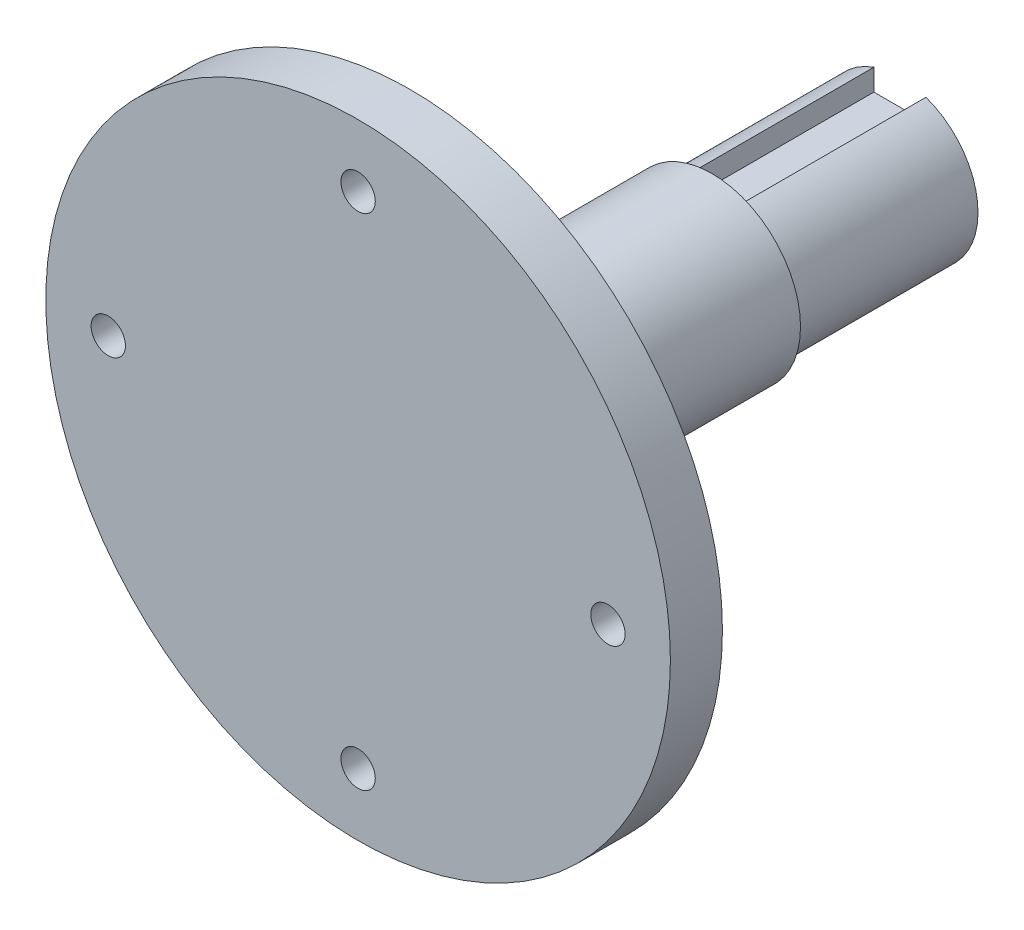
SolidWorks part; units mm, degrees
material "Plain Carbon Steel"
ref_plane "Front Plane" through (0, 0, 0) normal (0, 0, 1) x (1, 0, 0)
ref_plane "Top Plane" through (0, 0, 0) normal (0, 1, 0) x (1, 0, 0)
ref_plane "Right Plane" through (0, 0, 0) normal (1, 0, 0) x (0, 0, -1)
sketch "Sketch1" plane through (0, 0, 0) normal (0, 0, 1) x (1, 0, 0)
  circle A0 centre (0, 0) radius 7.5
  dimension "D1" = 15
extrude "Boss-Extrude1" add sketch "Sketch1" along normal blind 20.05
sketch "Sketch3" plane through (0, 0, 0) normal (0, 0, -1) x (-1, 0, 0)
  line L0 (0, 55) -> (0, -55) construction
  line L1 (-2.5, 5) -> (2.5, 5)
  line L2 (-2.5, 5) -> (-2.5, 10)
  line L3 (-2.5, 10) -> (2.5, 10)
  line L4 (2.5, 5) -> (2.5, 10)
  line L5 (-2.5, 5) -> (2.5, 10) construction
  line L6 (-2.5, 10) -> (2.5, 5) construction
  circle A0 centre (0, 0) radius 7.5 construction
  point P0 (0, 7.5)
  dimension "D1" = 2.5
  dimension "D2" = 5
extrude "Cut-Extrude1" cut sketch "Sketch3" against normal blind 21
sketch "Sketch6" plane through (0, 0, 20.05) normal (0, 0, 1) x (1, 0, 0)
  circle A0 centre (0, 0) radius 8.5
  dimension "D1" = 17
extrude "Boss-Extrude2" add sketch "Sketch6" along normal blind 24
sketch "Sketch7" plane through (0, 0, 44.05) normal (0, 0, 1) x (1, 0, 0)
  circle A0 centre (0, 0) radius 11.25
  dimension "D1" = 22.5
extrude "Boss-Extrude3" add sketch "Sketch7" along normal blind 5
sketch "Sketch8" plane through (0, 0, 49.05) normal (0, 0, 1) x (1, 0, 0)
  circle A0 centre (0, 0) radius 30
  dimension "D1" = 60
extrude "Boss-Extrude4" add sketch "Sketch8" along normal blind 5
fillet "Fillet1" radius 0.6 1 edges at (8.5, 0, 44.05)
fillet "Fillet2" radius 5 1 edges at (11.25, 0, 49.05)
hole_wizard "M4x0.7 Tapped Hole1" positions "Sketch9" profile "Sketch10" tap size "M4x0.7" standard "ANSI Metric" end condition through all
sketch "Sketch9" plane through (0, 0, 54.05) normal (0, 0, 1) x (1, 0, 0)
  circle A0 centre (0, 0) radius 24
  point P0 (0, 24)
  point P2 (0, -24)
  point P4 (24, 0)
  point P6 (-24, 0)
  dimension "D1" = 48
sketch "Sketch10" plane through (0, 24, 54.05) normal (1, 0, 0) x (0, -1, 0)
  line L0 (0, 0) -> (0, 54.05)
  line L1 (0, 54.05) -> (1.65, 54.05)
  line L2 (1.65, 54.05) -> (1.65, 0)
  line L5 (1.65, 0) -> (0, 0)
  line L11 (0, -6.35) -> (0, 107.95) construction
  dimension "Thru Tap Drill Dia." = 3.3
  dimension "Thru Tap Drill Depth" = 54.05
cosmetic thread "Hole Thread1" parameters "D2"=4
cosmetic thread "Hole Thread2" parameters "D2"=4
cosmetic thread "Hole Thread3" parameters "D2"=4
cosmetic thread "Hole Thread4" parameters "D2"=4
hole_wizard "M6x1.0 Tapped Hole2" positions "Sketch11" profile "Sketch12" tap size "M6x1.0" standard "ANSI Metric"
sketch "Sketch11" plane through (0, 0, 0) normal (0, 0, -1) x (-1, 0, 0)
  point P0 (0, 0)
sketch "Sketch12" plane through (0, 0, 0) normal (1, 0, 0) x (0, 1, 0)
  line L0 (0, 0) -> (0, 25)
  line L1 (0, 25) -> (2.5, 23.4978)
  line L2 (2.5, 23.4978) -> (2.5, 0)
  line L5 (2.5, 0) -> (0, 0)
  line L10 (0, 25) -> (-2.5, 23.4978) construction
  line L11 (0, -6.35) -> (0, 107.95) construction
  dimension "Tap Drill Dia." = 5
  dimension "Tap Drill Depth" = 25
  dimension "Drill Angle" = 118
cosmetic thread "Hole Thread5" parameters "D1"=20, "D2"=6
sketch "Sketch13" plane through (0, 0, 0) normal (0, 0, -1) x (-1, 0, 0)
  circle A0 centre (0, 0) radius 7.5
  dimension "D1" = 15
extrude "Cut-Extrude2" cut sketch "Sketch13" against normal blind 2
